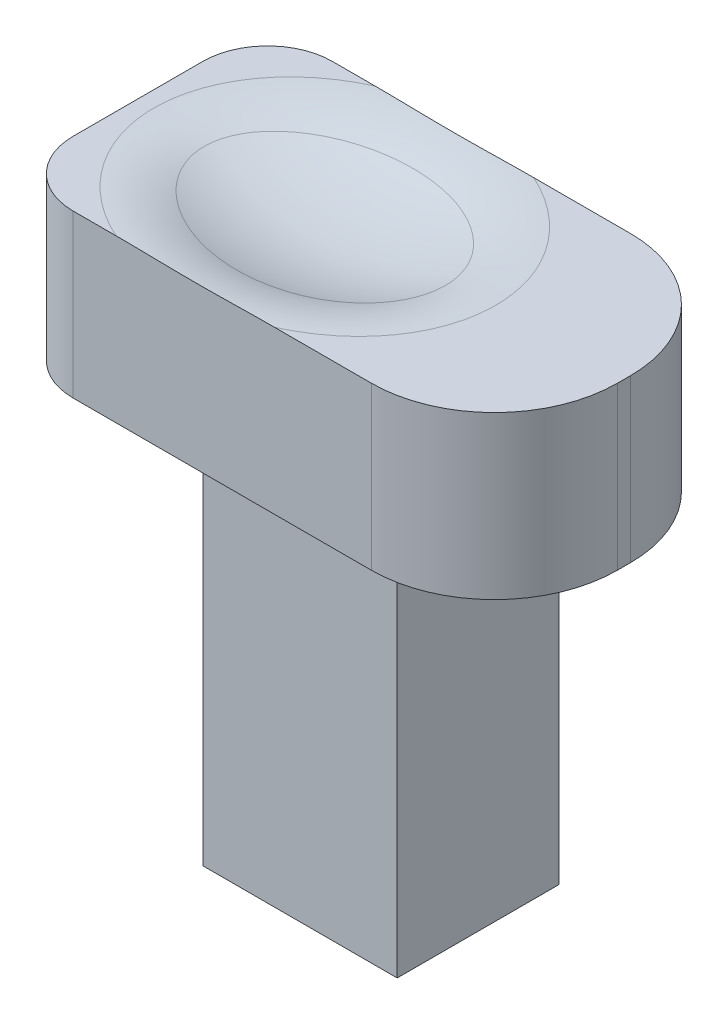
SolidWorks part; units mm, degrees
ref_plane "Front Plane" through (0, 0, 0) normal (0, 0, 1) x (1, 0, 0)
ref_plane "Top Plane" through (0, 0, 0) normal (0, 1, 0) x (1, 0, 0)
ref_plane "Right Plane" through (0, 0, 0) normal (1, 0, 0) x (0, 0, -1)
sketch "Sketch1" plane through (0, 0, 0) normal (0, 1, 0) x (1, 0, 0)
  line L1 (-3, 2.5) -> (3, 2.5)
  line L2 (-3, 2.5) -> (-3, -2.5)
  line L3 (-3, -2.5) -> (3, -2.5)
  line L4 (3, 2.5) -> (3, -2.5)
  dimension "D1" = 5
  dimension "D2" = 6
  dimension "D3" = 2.5
  dimension "D4" = 3
extrude "Boss-Extrude1" add sketch "Sketch1" along normal blind 12
shell "Shell1" thickness 0.75 removed face at (0, 0, 0)
sketch "Sketch2" plane through (0, 12, 0) normal (0, 1, 0) x (1, 0, 0)
  line L5 (3.7, 4) -> (-5.5, 4)
  line L6 (7.5, 0.2) -> (7.5, -0.2)
  line L7 (3.7, -4) -> (-5.5, -4)
  line L8 (-7.5, 2) -> (-7.5, -2)
  line L9 (7.5, 4) -> (-7.5, -4) construction
  line L10 (7.5, -4) -> (-7.5, 4) construction
  arc A0 (-5.5, 4) -> (-7.5, 2) centre (-5.5, 2) ccw
  arc A1 (-5.5, -4) -> (-7.5, -2) centre (-5.5, -2) cw
  arc A2 (7.5, -0.2) -> (3.7, -4) centre (3.7, -0.2) cw
  arc A3 (7.5, 0.2) -> (3.7, 4) centre (3.7, 0.2) ccw
  point P0 (0, 0)
  dimension "D3" = 2
  dimension "D4" = 3.8
  dimension "D5" = 3.8
  dimension "D1" = 15
  dimension "D2" = 8
extrude "Boss-Extrude2" add sketch "Sketch2" along normal blind 5
sketch "Sketch3" plane through (0, 0, 0) normal (0, 0, 1) x (1, 0, 0)
  line L0 (-6.1408, 17) -> (2.672, 17)
  line L1 (-5.5, 17) -> (-7.5, 17) construction
  line L2 (-5.5, 17) -> (3.7, 17) construction
  line L3 (-6.1408, 23.7178) -> (2.3516, 23.7178) construction
  arc A1 (-6.1408, 17) -> (2.672, 17) centre (-1.7344, 28.1195) ccw
  point P6 (2.6425, 16.9884)
revolve "Cut-Revolve2" cut sketch "Sketch3" angle 360 about L3
fillet "Fillet1" radius 5 1 edges at (-2.0129, 17, -3.4585)
sketch "Sketch4" plane through (0, 17, 0) normal (0, 1, 0) x (1, 0, 0)
  line L0 (-3.4515, 4) -> (-3.4515, -4)
  line L1 (0.7118, 4) -> (-4.1807, 4) construction
  line L2 (-4.1807, -4) -> (0.7118, -4) construction
  line L3 (-1.4515, 4) -> (-1.4515, -4)
  line L4 (0.5485, 4) -> (0.5485, -4)
  dimension "D1" = 2
  dimension "D2" = 2
